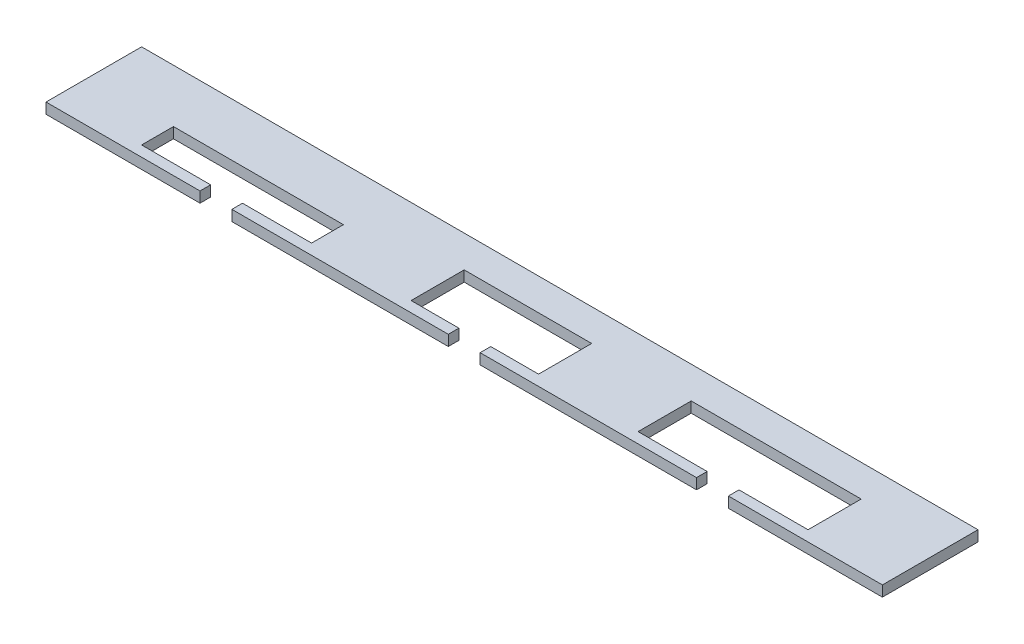
SolidWorks part; units mm, degrees
ref_plane "Front Plane" through (0, 0, 0) normal (0, 0, 1) x (1, 0, 0)
ref_plane "Top Plane" through (0, 0, 0) normal (0, 1, 0) x (1, 0, 0)
ref_plane "Right Plane" through (0, 0, 0) normal (1, 0, 0) x (0, 0, -1)
sketch "Sketch1" plane through (0, 0, 0) normal (0, 1, 0) x (1, 0, 0)
  line L0 (0, 57.15) -> (304.8, 57.15) construction
  line L2 (0, 0) -> (0, 114.3)
  line L3 (0, 114.3) -> (1000.0005, 114.3)
  line L4 (1000.0005, 0) -> (1000.0005, 114.3)
  line L9 (101.6, 12.7) -> (184.15, 12.7)
  line L10 (101.6, 12.7) -> (101.6, 50.8)
  line L12 (304.8, 12.7) -> (304.8, 50.8)
  line L17 (0, -31.5189) -> (406.4, -31.5189) construction
  line L18 (0, -31.5189) -> (0, -107.7189) construction
  line L19 (0, -107.7189) -> (406.4, -107.7189) construction
  line L20 (406.4, -31.5189) -> (406.4, -107.7189) construction
  line L21 (593.6005, -31.5189) -> (1000.0005, -31.5189) construction
  line L22 (593.6005, -31.5189) -> (593.6005, -107.7189) construction
  line L23 (593.6005, -107.7189) -> (1000.0005, -107.7189) construction
  line L24 (1000.0005, -31.5189) -> (1000.0005, -107.7189) construction
  line L25 (203.2, -31.5189) -> (203.2, -107.7189) construction
  line L26 (796.8005, -107.7189) -> (796.8005, -31.5189) construction
  line L27 (203.2, -31.5189) -> (203.2, 114.3) construction
  line L28 (796.8005, -31.5189) -> (796.8005, 114.3) construction
  line L29 (500.0003, -101.6) -> (500.0003, 12.7813) construction
  line L30 (0, 0) -> (184.15, 0)
  line L35 (101.6, 50.8) -> (304.8, 50.8)
  line L36 (423.8003, 76.2) -> (576.2003, 76.2)
  line L37 (423.8003, 76.2) -> (423.8003, 12.7)
  line L38 (423.8003, 12.7) -> (480.9503, 12.7)
  line L39 (576.2003, 76.2) -> (576.2003, 12.7)
  line L43 (898.4005, 12.7) -> (815.8505, 12.7)
  line L44 (898.4005, 12.7) -> (898.4005, 76.2)
  line L46 (550.8003, 0) -> (777.7505, 0)
  line L48 (203.2, 12.7813) -> (184.15, 12.7813) construction
  line L49 (203.2, 12.7813) -> (222.25, 12.7813) construction
  line L50 (184.15, 12.7) -> (184.15, 0)
  line L51 (222.25, 12.7) -> (222.25, 0)
  line L52 (222.25, 12.7) -> (304.8, 12.7)
  line L53 (222.25, 0) -> (449.2003, 0)
  line L54 (796.8005, 12.7813) -> (777.7505, 12.7813) construction
  line L55 (796.8005, 12.7813) -> (815.8505, 12.7813) construction
  line L56 (777.7505, 12.7) -> (777.7505, 0)
  line L57 (815.8505, 12.7) -> (815.8505, 0)
  line L58 (815.8505, 0) -> (1000.0005, 0)
  line L59 (777.7505, 12.7) -> (695.2005, 12.7)
  line L60 (480.9503, 12.7813) -> (519.0503, 12.7813) construction
  line L61 (480.9503, 12.7) -> (480.9503, 0)
  line L62 (480.9503, 0) -> (449.2003, 0)
  line L63 (519.0503, 12.7) -> (519.0503, 0)
  line L64 (519.0503, 0) -> (550.8003, 0)
  line L65 (519.0503, 12.7) -> (576.2003, 12.7)
  line L66 (898.4005, 76.2) -> (695.2005, 76.2)
  line L67 (695.2005, 76.2) -> (695.2005, 12.7)
  line L68 (695.2005, 57.15) -> (1000.0005, 57.15) construction
  line L69 (500.0003, 76.2) -> (500.0003, 114.3) construction
  point P36 (500.0003, 57.15)
  point P57 (500.0003, 12.7813)
  dimension "D1" = 406.4
  dimension "D2" = 76.2
  dimension "D3" = 1000.0005
  dimension "D4" = 63.5
  dimension "D5" = 38.1
  dimension "D6" = 203.2
  dimension "D7" = 38.1
  dimension "D8" = 19.05
  dimension "D9" = 19.05
  dimension "D10" = 152.4
  dimension "D11" = 63.5
  dimension "D12" = 12.7
  dimension "D13" = 12.7
  dimension "D14" = 184.15
  dimension "D15" = 101.6
  dimension "D16" = 38.1
extrude "Boss-Extrude1" add sketch "Sketch1" along normal blind 12.7
